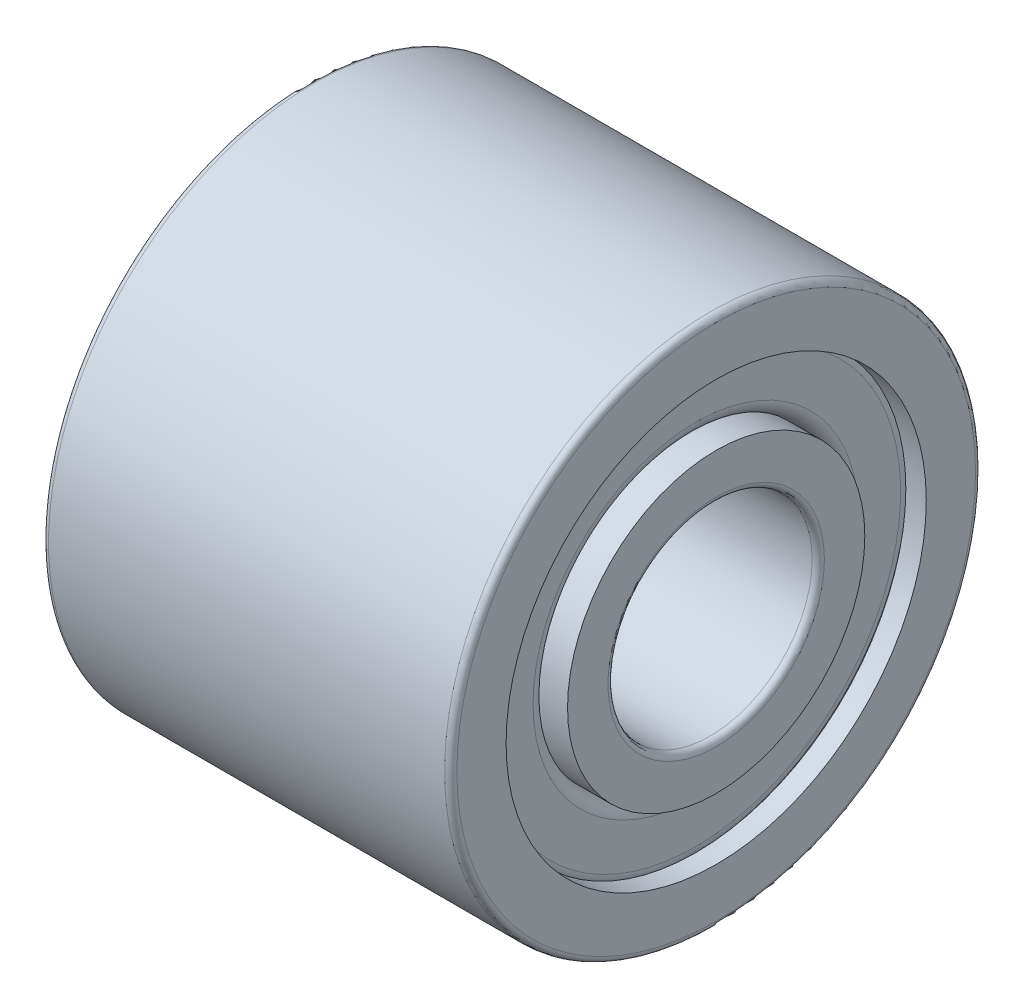
SolidWorks part; units mm, degrees
ref_plane "Plane1" through (0, 0, 0) normal (0, 0, 1) x (1, 0, 0)
ref_plane "Plane2" through (0, 0, 0) normal (0, 1, 0) x (1, 0, 0)
ref_plane "Plane3" through (0, 0, 0) normal (1, 0, 0) x (0, 0, -1)
other "Configuration Table"
sketch "Clipboard" plane through (0, 0, 0) normal (0, 0, 1) x (1, 0, 0)
  line L0 (-10, 0) -> (10, 0) construction
  line L1 (0, 0) -> (7.2756, -0.2541)
  line L2 (0, 0) -> (8.9945, 0.3141)
  line L3 (0, 0) -> (10.7135, -0.3741)
  line L4 (0, 0) -> (-22.3573, -0.3902)
  dimension "Race_OD" = 10.72
  dimension "Race_ID" = 7.28
sketch "OutRacSke" plane through (0, 0, 0) normal (0, 0, 1) x (1, 0, 0)
  line L0 (-4.5, 5.36) -> (-4.5, 5.145)
  line L1 (-4.5, 5.145) -> (-5, 5.145)
  line L2 (-5, 5.145) -> (-5, 6.35)
  line L3 (-4.85, 6.5) -> (4.85, 6.5)
  line L4 (5, 6.35) -> (5, 5.145)
  line L5 (5, 5.145) -> (4.5, 5.145)
  line L6 (4.5, 5.145) -> (4.5, 5.36)
  line L7 (4.5, 5.36) -> (-4.5, 5.36)
  line L8 (-7.9375, 0) -> (7.9375, 0) construction
  arc A0 (-5, 6.35) -> (-4.85, 6.5) centre (-4.85, 6.35) cw
  arc A1 (4.85, 6.5) -> (5, 6.35) centre (4.85, 6.35) cw
  dimension "D1" = 4.5
  dimension "Groove_Dp" = 0.215
  dimension "Race_OD" = 10.72
  dimension "Cyl_Len" = 9
  dimension "halfWidth" = 5
revolve "OuterRace" add sketch "OutRacSke" angle 360 about L8 reverse direction yes
sketch "RolDetSke" plane through (0, 0, 0) normal (0, 0, 1) x (1, 0, 0)
  line L0 (-4.5, 5.0163) -> (-4.5, 4.5)
  line L1 (-4.5, 4.5) -> (4.5, 4.5)
  line L2 (4.5, 4.5) -> (4.5, 5.0163)
  line L3 (4.1558, 5.3605) -> (-4.1558, 5.3605)
  line L4 (-28.575, 4.5) -> (28.575, 4.5) construction
  arc A0 (4.5, 5.0163) -> (4.1558, 5.3605) centre (4.1558, 5.0163) ccw
  arc A1 (-4.1558, 5.3605) -> (-4.5, 5.0163) centre (-4.1558, 5.0163) ccw
  dimension "Cyl_Len" = 9
  dimension "radius" = 0.3442
  dimension "Roller_diameter" = 1.721
revolve "RollerDetailed" [suppressed] add sketch "RolDetSke" angle 360 about L4 reverse direction yes
ref_axis "Axis1" through (-50, 0, 0) along (1, 0, 0)
sketch "RolSimSke" plane through (0, 25.4, 0) normal (0, 0, 1) x (1, 0, 0)
  line L0 (-4.5, -20.3832) -> (-4.5, -21.4158)
  line L1 (-25.4, -25.4) -> (25.4, -25.4) construction
  line L2 (4.5, -21.4158) -> (4.5, -20.3832)
  line L3 (4.1558, -20.039) -> (-4.1558, -20.039)
  line L5 (4.1558, -21.76) -> (-4.1558, -21.76)
  arc A0 (4.5, -20.3832) -> (4.1558, -20.039) centre (4.1558, -20.3832) ccw
  arc A1 (-4.1558, -20.039) -> (-4.5, -20.3832) centre (-4.1558, -20.3832) ccw
  arc A2 (4.5, -21.4158) -> (4.1558, -21.76) centre (4.1558, -21.4158) cw
  arc A3 (-4.1558, -21.76) -> (-4.5, -21.4158) centre (-4.1558, -21.4158) cw
  dimension "Cyl_Len" = 9
  dimension "radius" = 0.3442
  dimension "Roller_diameter" = 1.721
revolve "RollersSimplified" add sketch "RolSimSke" angle 360 about L1
sketch "InsRacSke" plane through (0, 0, 0) normal (0, 0, 1) x (1, 0, 0)
  line L2 (-5, 3.64) -> (-5, 2.65)
  line L4 (-4.85, 2.5) -> (4.85, 2.5)
  line L5 (5, 2.65) -> (5, 3.64)
  line L8 (5, 3.64) -> (-5, 3.64)
  line L9 (-7.9375, 0) -> (7.9375, 0) construction
  arc A0 (-5, 2.65) -> (-4.85, 2.5) centre (-4.85, 2.65) ccw
  arc A2 (4.85, 2.5) -> (5, 2.65) centre (4.85, 2.65) ccw
  dimension "radius" = 0.15
  dimension "Bore" = 5
  dimension "halfWidth" = 5
  dimension "Race_ID" = 7.28
revolve "InnerRace" add sketch "InsRacSke" angle 360 about L9 reverse direction yes
sketch "CagSpiSke" plane through (0, 0, 0) normal (0, 0, 1) x (1, 0, 0)
  line L0 (-17.1595, 0) -> (17.1595, 0) construction
  line L3 (-4.75, 4.3279) -> (4.75, 4.3279)
  line L4 (-4.75, 4.3279) -> (-4.75, 4.6721)
  line L5 (-4.75, 4.6721) -> (4.75, 4.6721)
  line L6 (4.75, 4.3279) -> (4.75, 4.6721)
revolve "CageSpine" [suppressed] add sketch "CagSpiSke" angle 0.001 about L0
pattern_circular "RollersDetailed" [suppressed] count 2 every 180 about axis through (-50, 0, 0) along (1, 0, 0)
equation "\"halfWidth@OutRacSke\" =  \"Width@OutRacSke\" / 2"
equation "\"CLdia@Clipboard\" =  ( \"Race_OD@Clipboard\" + \"Race_ID@Clipboard\" )  / 2"
equation "\"CLRad@RolDetSke\" = ( \"Race_OD@Clipboard\" + \"Race_ID@Clipboard\" )  / 4"
equation "\"Roller_diameter@RolDetSke\" =  ( \"Race_OD@Clipboard\" -  \"Race_ID@Clipboard\" )  / 2 + .001"
equation "\"Roller_diameter@RolSimSke\" = ( \"Race_OD@Clipboard\" -  \"Race_ID@Clipboard\" )  / 2 + .001"
equation "\"radius@RolDetSke\" = \"Roller_diameter@RolDetSke\" / 5"
equation "\"radius@RolSimSke\" = \"Roller_diameter@RolSimSke\" / 5"
equation "\"Cyl_Len@OutRacSke\" = \"Cyl_Len@RolDetSke\""
equation "\"Cyl_Len@RolSimSke\" = \"Cyl_Len@RolDetSke\""
equation "\"halfCylLen@RolDetSke\" = \"Cyl_Len@RolDetSke\" / 2"
equation "\"D1@OutRacSke\" = \"Cyl_Len@OutRacSke\" / 2"
equation "\"cage_width@CagSpiSke\" =  ( \"Cyl_Len@RolDetSke\" + \"Width@OutRacSke\" )  / 2"
equation "\"halfwidth@CagSpiSke\" = \"cage_width@CagSpiSke\" / 2"
equation "\"cage_thickness@CagSpiSke\" = \"Roller_diameter@RolDetSke\" / 5"
equation "\"d2@CagSpiSke\" = \"CLRad@RolDetSke\" * 2 - \"cage_thickness@CagSpiSke\""
equation "\"Max_count@Clipboard\" = int( 3.14159265 / atn(( \"Roller_diameter@RolDetSke\" / 2) / sqr( \"CLRad@RolDetSke\"  *  \"CLRad@RolDetSke\" - ( \"Roller_diameter@RolDetSke\" / 2) *  ( \"Roller_diameter@RolDetSke\" / 2))))"
equation "\"Max_count@Clipboard\" = ((sgn( \"Max_count@Clipboard\" - \"Count@Clipboard\" )-1)*( \"Max_count@Clipboard\" - \"Count@Clipboard\" ))/-2+ \"Count@Clipboard\""
equation "\"Count@RollersDetailed\" = int( \"Show_count@Clipboard\" ) "
equation "\"Count@RollersDetailed\" = ((sgn( \"Count@RollersDetailed\" - \"Max_count@Clipboard\" )-1)*( \"Count@RollersDetailed\" - \"Max_count@Clipboard\" ))/-2+ \"Max_count@Clipboard\""
equation "\"Count@RollersDetailed\" = ((sgn( \"Count@RollersDetailed\" - \"Min_count@Clipboard\" )+1)*( \"Count@RollersDetailed\" - \"Min_count@Clipboard\"))/2 +\"Min_count@Clipboard\""
equation "\"Angle@RollersDetailed\" = 360.0 / \"Max_count@Clipboard\""
equation "\"Bore@RolSimSke\" = \"Race_ID@Clipboard\""
equation "\"Race_ID@InsRacSke\" = \"Race_ID@Clipboard\""
equation "\"halfWidth@InsRacSke\" = \"Width_IR@InsRacSke\" / 2"
equation "\"halfLength@RolSimSke\" = \"Cyl_Len@RolSimSke\" / 2"
equation "\"Race_OD@OutRacSke\" = \"Race_OD@Clipboard\""
equation "\"Width_IR@InsRacSke\" = \"Width@OutRacSke\""
equation "\"Angle@CageSpine\" =  \"Angle@RollersDetailed\" * ( \"Count@RollersDetailed\" -1 + int( \"Count@RollersDetailed\" / \"Max_count@Clipboard\" ) )  + 0.001 -  int( \"Count@RollersDetailed\" / \"Max_count@Clipboard\" ) * 0.001"
equation "\"Angle@CageSpine\" =  \"Angle@CageSpine\" * int( \"Min_count@Clipboard\" / 2) + int(1 / \"Min_count@Clipboard\")  * 0.001"
equation "\"radius@InsRacSke\" = \"Radius@OutRacSke\""
